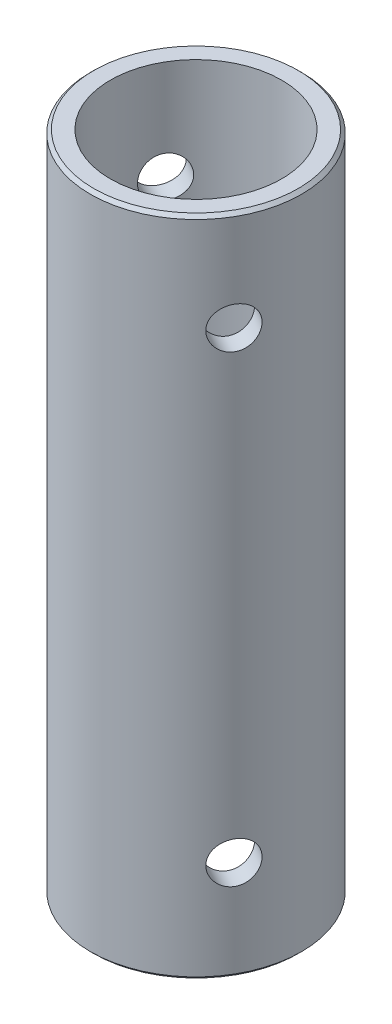
SolidWorks part; units mm, degrees
ref_plane "Front Plane" through (0, 0, 0) normal (0, 0, 1) x (1, 0, 0)
ref_plane "Top Plane" through (0, 0, 0) normal (0, 1, 0) x (1, 0, 0)
ref_plane "Right Plane" through (0, 0, 0) normal (1, 0, 0) x (0, 0, -1)
sketch "Sketch1" plane through (0, 0, 0) normal (0, 1, 0) x (1, 0, 0)
  circle A0 centre (0, 0) radius 7.94
  circle A1 centre (0, 0) radius 6.44
  dimension "D1" = 15.88
  dimension "D2" = 1.5
extrude "Boss-Extrude1" add sketch "Sketch1" along normal blind 49.82
chamfer "Chamfer1" distance 0.25 angle 45 2 edges at (0, 0, 7.94) (0, 49.82, 7.94)
sketch "Sketch2" plane through (-5.0662, 0, -2.925) normal (-0.866, 0, -0.5) x (-0.5, 0, 0.866)
  circle A0 centre (0, 7.5) radius 1.55 construction
  circle A1 centre (0, 7.5) radius 1.55
extrude "Cut-Extrude1" cut sketch "Sketch2" against normal through all both and the other way through all
sketch "Sketch3" plane through (-5.0662, 0, -2.925) normal (-0.866, 0, -0.5) x (-0.5, 0, 0.866)
  circle A0 centre (0, 42.32) radius 1.55 construction
  circle A1 centre (0, 42.32) radius 1.55
extrude "Cut-Extrude2" cut sketch "Sketch3" against normal through all both and the other way through all
